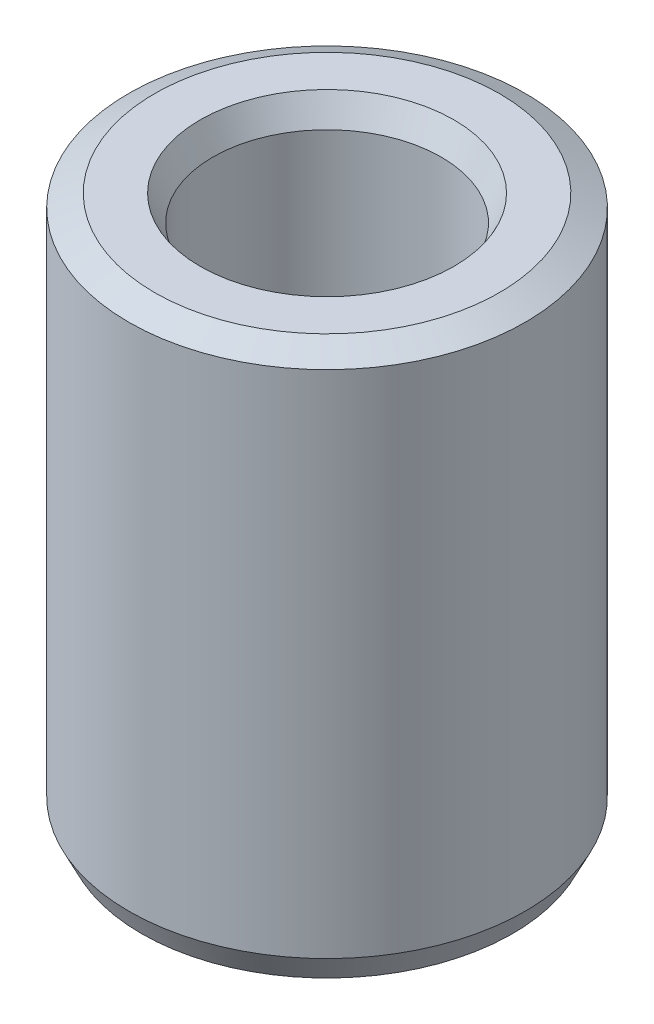
SolidWorks part; units mm, degrees
ref_plane "Front Plane" through (0, 0, 0) normal (0, 0, 1) x (1, 0, 0)
ref_plane "Top Plane" through (0, 0, 0) normal (0, 1, 0) x (1, 0, 0)
ref_plane "Right Plane" through (0, 0, 0) normal (1, 0, 0) x (0, 0, -1)
sketch "Sketch1" plane through (0, 0, 0) normal (0, 1, 0) x (1, 0, 0)
  circle A0 centre (0, 0) radius 57.5
  dimension "SLEEVE_OD" = 115
extrude "Boss-Extrude1" add sketch "Sketch1" along normal blind 159.112
sketch "Sketch2" plane through (0, 0, 0) normal (0, 1, 0) x (1, 0, 0)
  circle A0 centre (0, 0) radius 33.117
  dimension "BORE_D" = 66.2341
extrude "Cut-Extrude1" cut sketch "Sketch2" along normal through all
chamfer "Chamfer1" distance 3.6932 angle 63.777 4 edges at (0, 159.112, 33.117) (0, 0, 33.117) (0, 0, 57.5) (0, 159.112, 57.5) first distance on face at (0, 159.112, 33.117) first distance on face at (0, 0, 33.117) first distance on face at (0, 159.112, 57.5)
